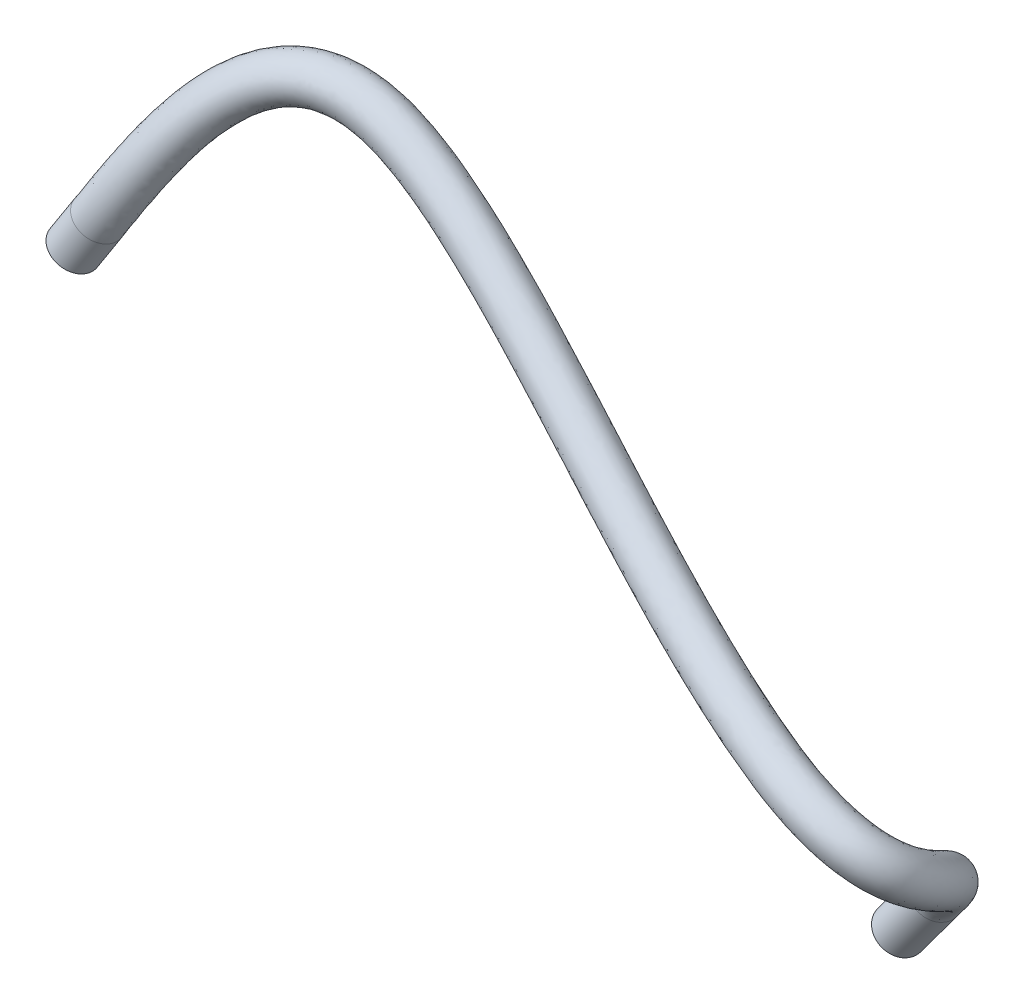
SolidWorks part; units mm, degrees
material "Silicon Rubber"
ref_plane "X-Y Datum" through (0, 0, 0) normal (0, 0, 1) x (1, 0, 0)
ref_plane "X-Z Datum" through (0, 0, 0) normal (0, 1, 0) x (1, 0, 0)
ref_plane "Y-Z Datum" through (0, 0, 0) normal (1, 0, 0) x (0, 0, -1)
sketch3d "3DSketch1"
  line L0 (227.4183, 284.9582, 17.6068) -> (250.1359, 315.5445, 17.6068)
  line L1 (-227.3844, 465.5111, 63.1578) -> (-240.4946, 443.8709, 65.3905)
  line L2 (-227.3844, 465.5111, 63.1578) -> (-240.4946, 443.8709, 65.3905) construction
  line L3 (-293.7612, 355.947, 74.462) -> (-279.8252, 378.9503, 72.0886) construction
  line L4 (247.2962, 311.7212, 17.6068) -> (250.1359, 315.5445, 17.6068) construction
  circle A0 centre (247.2962, 311.7212, 17.6068) radius 12.3825 construction
  circle A4 centre (-279.8252, 378.9503, 72.0886) radius 8 construction
  circle A5 centre (-293.7612, 355.947, 74.462) radius 10 construction
  circle A10 centre (250.1359, 315.5445, 17.6068) radius 6.985 construction
  circle A14 centre (247.2962, 311.7212, 17.6068) radius 12.3825 construction
  circle A15 centre (250.1359, 315.5445, 17.6068) radius 6.985 construction
  circle A16 centre (-279.8252, 378.9503, 72.0886) radius 8 construction
  circle A17 centre (-293.7612, 355.947, 74.462) radius 10 construction
  spline S0 degree 3 poles (250.1359, 315.5445, 17.6068) (275.2465, 349.3526, 17.6068) (325.2229, 375.0711, 116.6813) (84.2085, 435.8751, 46.4568) (-150.7758, 635.9123, -20.0486) (-193.2064, 521.9265, 57.3372) (-227.3844, 465.5111, 63.1578) knots 0 0 0 0 0.305815 0.372417 0.666027 1 1 1 1
  point P1 (-174.876, 529.8828, 27.7942)
  point P4 (0, 0, 0)
  point P5 (-162.403, 552.936, 41.4232)
  point P6 (-99.9018, 559.7497, 13.9161)
  point P10 (-275.696, 385.7661, 71.3854)
  point P14 (-288.5997, 364.4667, 73.583)
  point P16 (239.913, 301.7807, 17.6068)
  point P19 (245.971, 309.937, 17.6068)
  point P21 (239.913, 301.7807, 17.6068)
  point P24 (245.971, 309.937, 17.6068)
  point P26 (-275.696, 385.7661, 71.3854)
  point P29 (-288.5997, 364.4667, 73.583)
  dimension "D2" = 38.1
  dimension "D1" = 25.4
  dimension "D3" = 76.2
sweep "Sweep1" add path "3DSketch1" circular profile diameter 26.9875 parameters "D3"=26.9875
sweep "Cut-Sweep1" cut path "3DSketch1<2>" circular profile diameter 19.05 parameters "D3"=19.05
sketch3d "3DSketch1<2>" same geometry as "3DSketch1"
